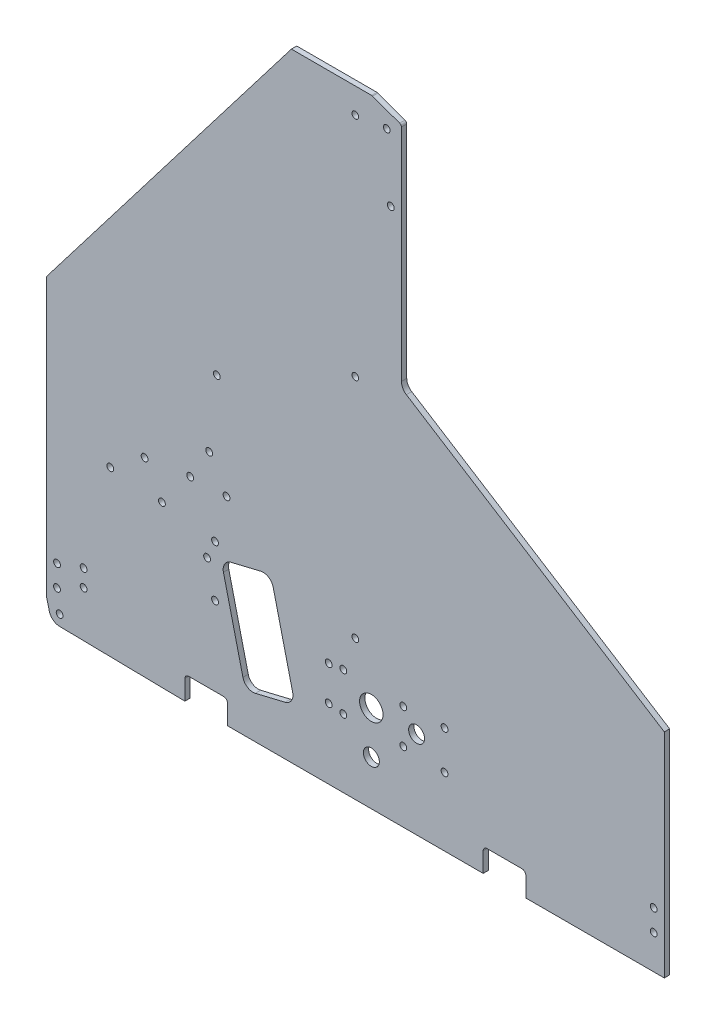
SolidWorks part; units mm, degrees
ref_plane "Front Plane" through (0, 0, 0) normal (0, 0, 1) x (1, 0, 0)
ref_plane "Top Plane" through (0, 0, 0) normal (0, 1, 0) x (1, 0, 0)
ref_plane "Right Plane" through (0, 0, 0) normal (1, 0, 0) x (0, 0, -1)
sketch "Sketch1" plane through (0, 0, 0) normal (0, 0, 1) x (1, 0, 0)
  line L0 (82.55, -20.32) -> (82.55, -6.35)
  line L2 (0, 0) -> (0, 157.48)
  line L4 (368.3, -20.32) -> (368.3, 106.68)
  line L5 (82.55, -6.35) -> (107.95, -6.35)
  line L6 (107.95, -6.35) -> (107.95, -20.32)
  line L7 (107.95, -20.32) -> (260.35, -20.32)
  line L8 (260.35, -20.32) -> (260.35, -6.35)
  line L9 (260.35, -6.35) -> (285.75, -6.35)
  line L10 (285.75, -6.35) -> (285.75, -20.32)
  line L11 (285.75, -20.32) -> (368.3, -20.32)
  line L12 (361.95, 12.7) -> (368.3, 12.7) construction
  line L13 (0, 0) -> (6.35, 0) construction
  line L14 (0.1896, -7.8901) -> (1.7771, -14.2401)
  line L15 (7.8295, -19.0491) -> (82.55, -20.32)
  line L16 (0, 0) -> (0, -6.35)
  line L17 (85.725, 97.155) -> (82.9754, 95.5675) construction
  line L18 (97.0634, 115.6163) -> (58.5686, 93.3913) construction
  line L19 (97.0634, 115.6163) -> (107.3822, 97.7437) construction
  line L20 (58.5686, 93.3913) -> (68.8873, 75.5187) construction
  line L21 (107.3822, 97.7437) -> (68.8873, 75.5187) construction
  line L22 (97.0634, 115.6163) -> (68.8873, 75.5187) construction
  line L23 (58.5686, 93.3913) -> (107.3822, 97.7437) construction
  line L24 (7.9375, -12.7) -> (95.7973, 60.4105) construction
  line L25 (184.15, 62.98) -> (184.15, 197.98) construction
  line L26 (184.15, 197.98) -> (184.15, 332.98) construction
  line L27 (355.6, 335.28) -> (330.2, 335.28) construction
  line L28 (330.2, 335.28) -> (330.2, 220.98) construction
  line L29 (330.2, 220.98) -> (355.6, 220.98) construction
  line L30 (355.6, 220.98) -> (355.6, 335.28) construction
  line L31 (184.15, 347.98) -> (184.15, 269.4703) construction
  line L32 (12.7, 335.28) -> (38.1, 335.28) construction
  line L33 (38.1, 335.28) -> (38.1, 220.98) construction
  line L34 (12.7, 220.98) -> (12.7, 335.28) construction
  line L35 (38.1, 220.98) -> (12.7, 220.98) construction
  line L36 (194.15, 347.98) -> (211.6138, 341.63)
  line L37 (184.15, 347.98) -> (146.05, 347.98)
  line L38 (184.15, 347.98) -> (194.15, 347.98)
  line L39 (348.5362, 347.98) -> (413.4623, 347.98)
  line L40 (348.5362, 347.98) -> (211.6138, 347.98) construction
  line L42 (146.05, 347.98) -> (0, 157.48)
  line L44 (211.6138, 341.63) -> (211.6138, 205.74)
  line L45 (211.6138, 205.74) -> (368.3, 106.68)
  line L46 (194.15, 347.98) -> (-141.0713, 347.98) construction
  circle A0 centre (6.35, 0) radius 2.032
  circle A1 centre (6.35, 12.7) radius 2.032
  circle A2 centre (361.95, 0) radius 2.032
  circle A3 centre (361.95, 12.7) radius 2.032
  arc A5 (1.7771, -14.2401) -> (7.8295, -19.0491) centre (7.9375, -12.7) ccw
  circle A6 centre (7.9375, -12.7) radius 2.032
  arc A7 (0, -6.35) -> (0.1896, -7.8901) centre (6.35, -6.35) ccw
  circle A8 centre (38.1, 78.105) radius 2.032
  circle A9 centre (85.725, 97.155) radius 2.032
  circle A10 centre (58.5686, 93.3913) radius 2.032
  circle A11 centre (68.8873, 75.5187) radius 2.032
  circle A12 centre (107.3822, 97.7437) radius 2.032
  circle A13 centre (97.0634, 115.6163) radius 2.032
  circle A14 centre (95.7973, 60.4105) radius 2.032
  circle A15 centre (184.15, 62.98) radius 2
  circle A16 centre (184.15, 197.98) radius 2
  circle A17 centre (184.15, 332.98) radius 2
  circle A18 centre (63.5, 316.23) radius 2.032
  circle A19 centre (101.6, 157.48) radius 2.032
  circle A20 centre (355.6, 335.28) radius 2.032
  circle A21 centre (330.2, 335.28) radius 2.032
  circle A22 centre (355.6, 220.98) radius 2.032
  circle A23 centre (330.2, 220.98) radius 2.032
  circle A24 centre (12.7, 335.28) radius 2.032
  circle A25 centre (38.1, 335.28) radius 2.032
  circle A26 centre (12.7, 220.98) radius 2.032
  circle A27 centre (38.1, 220.98) radius 2.032
  circle A28 centre (202.8819, 335.28) radius 2
  circle A29 centre (205.2638, 296.418) radius 2.032
  point P82 (184.15, 347.98)
  point P83 (202.8819, 344.805)
  dimension "D6" = 4.064
  dimension "D10" = 6.35
  dimension "D11" = 4.064
  dimension "D17" = 38.1
  dimension "D27" = 4
  dimension "D31" = 4.064
  dimension "D32" = 38.1
  dimension "D36" = 4.064
  dimension "D47" = 45.212
  dimension "D48" = 4.064
  dimension "D2" = 127
  dimension "D3" = 13.97
  dimension "D4" = 25.4
  dimension "D5" = 152.4
  dimension "D7" = 12.7
  dimension "D8" = 6.35
  dimension "D9" = 20.32
  dimension "D12" = 12.7
  dimension "D13" = 1.5875
  dimension "D14" = 82.55
  dimension "D15" = 368.3
  dimension "D16" = 6.35
  dimension "D18" = 98.425
  dimension "D19" = 47.625
  dimension "D20" = 19.05
  dimension "D21" = 3.175
  dimension "D22" = 60
  dimension "D23" = 20.6375
  dimension "D24" = 44.45
  dimension "D25" = 38.1
  dimension "D26" = 114.3
  dimension "D28" = 135
  dimension "D29" = 12.7
  dimension "D30" = 15
  dimension "D33" = 63.5
  dimension "D34" = 27.4638
  dimension "D35" = 101.6
  dimension "D37" = 114.3
  dimension "D38" = 25.4
  dimension "D39" = 12.7
  dimension "D40" = 157.48
  dimension "D41" = 142.24
  dimension "D42" = 368.3
  dimension "D43" = 10
  dimension "D44" = 6.35
  dimension "D45" = 31.75
  dimension "D46" = 6.35
  dimension "D49" = 6.35
extrude "Boss-Extrude1" add sketch "Sketch1" along normal blind 3.175 contours L16 A7 L14 A5 L15 L2 A0 A1 A6 region at (167.8922, 118.3155, 0)
fillet "Fillet1" radius 2.286 4 edges at (285.75, -6.35, 1.5875) (107.95, -6.35, 1.5875) (260.35, -6.35, 1.5875) (82.55, -6.35, 1.5875)
fillet "Fillet2" radius 6.35 1 edges at (211.6138, 205.74, 1.5875)
sketch "Sketch2" plane through (0, 0, 0) normal (0, 0, -1) x (-1, 0, 0)
  circle A0 centre (-100.5528, 71.086) radius 2.032 construction
  circle A1 centre (-100.5528, 40.606) radius 2.032 construction
  circle A2 centre (-22.225, 18.2025) radius 2.032 construction
  circle A3 centre (-22.225, 8.0425) radius 2.032 construction
  circle A4 centre (-100.5528, 71.086) radius 2.032
  circle A5 centre (-100.5528, 40.606) radius 2.032
  circle A6 centre (-22.225, 18.2025) radius 2.032
  circle A7 centre (-22.225, 8.0425) radius 2.032
extrude "Cut-Extrude1" cut sketch "Sketch2" against normal through all
fillet "Fillet3" radius 1.5875 2 edges at (211.6138, 341.63, 1.5875) (194.15, 347.98, 1.5875)
sketch "Sketch3" plane through (0, 0, 3.175) normal (0, 0, 1) x (1, 0, 0)
  line L0 (132.9524, 63.2646) -> (132.7215, 64.2281) construction
  line L1 (128.3814, 66.8897) -> (110.6828, 62.6472) construction
  line L2 (114.5132, 58.4237) -> (126.8822, 61.3887) construction
  line L3 (108.0212, 58.3071) -> (108.2522, 57.3436) construction
  line L4 (131.2006, 57.703) -> (140.0164, 20.9265) construction
  line L5 (144.0993, 16.7636) -> (132.9524, 63.2646) construction
  line L6 (108.2522, 57.3436) -> (119.3991, 10.8426) construction
  line L7 (121.1509, 16.4042) -> (112.3351, 53.1807) construction
  line L8 (119.3991, 10.8426) -> (119.6301, 9.8791) construction
  line L9 (144.3303, 15.8001) -> (144.0993, 16.7636) construction
  line L10 (137.8383, 15.6835) -> (125.4694, 12.7185) construction
  line L11 (123.9701, 7.2175) -> (141.6687, 11.4601) construction
  line L12 (132.9524, 63.2646) -> (132.7215, 64.2281)
  line L13 (128.3814, 66.8897) -> (110.6828, 62.6472)
  line L14 (114.5132, 58.4237) -> (126.8822, 61.3887)
  line L15 (108.0212, 58.3071) -> (108.2522, 57.3436)
  line L16 (131.2006, 57.703) -> (140.0164, 20.9265)
  line L17 (144.0993, 16.7636) -> (132.9524, 63.2646)
  line L18 (108.2522, 57.3436) -> (119.3991, 10.8426)
  line L19 (121.1509, 16.4042) -> (112.3351, 53.1807)
  line L20 (119.3991, 10.8426) -> (119.6301, 9.8791)
  line L21 (144.3303, 15.8001) -> (144.0993, 16.7636)
  line L22 (137.8383, 15.6835) -> (125.4694, 12.7185)
  line L23 (123.9701, 7.2175) -> (141.6687, 11.4601)
  line L24 (127.7894, 69.3598) -> (110.0908, 65.1172)
  line L25 (105.5512, 57.715) -> (105.7822, 56.7515)
  line L26 (105.7822, 56.7515) -> (116.9291, 10.2505)
  line L27 (116.9291, 10.2505) -> (117.16, 9.287)
  line L28 (124.5622, 4.7475) -> (142.2608, 8.99)
  line L29 (146.8003, 16.3922) -> (146.5694, 17.3557)
  line L30 (146.5694, 17.3557) -> (135.4225, 63.8567)
  line L31 (135.4225, 63.8567) -> (135.1915, 64.8202)
  arc A0 (132.7215, 64.2281) -> (128.6308, 66.9403) centre (129.2206, 63.3889) ccw construction
  arc A1 (110.6828, 62.6472) -> (110.4377, 62.5791) centre (111.522, 59.1463) ccw construction
  arc A2 (128.6308, 66.9403) -> (128.3814, 66.8897) centre (129.2206, 63.3889) ccw construction
  arc A3 (110.4377, 62.5791) -> (108.0212, 58.3071) centre (111.522, 59.1463) ccw construction
  arc A4 (119.6301, 9.8791) -> (123.7207, 7.1669) centre (123.1309, 10.7183) ccw construction
  arc A5 (141.9139, 11.5281) -> (144.3303, 15.8001) centre (140.8295, 14.9609) ccw construction
  arc A6 (141.6687, 11.4601) -> (141.9139, 11.5281) centre (140.8295, 14.9609) ccw construction
  arc A7 (123.7207, 7.1669) -> (123.9701, 7.2175) centre (123.1309, 10.7183) ccw construction
  arc A8 (132.7215, 64.2281) -> (128.6308, 66.9403) centre (129.2206, 63.3889) ccw
  arc A9 (110.6828, 62.6472) -> (110.4377, 62.5791) centre (111.522, 59.1463) ccw
  arc A10 (128.6308, 66.9403) -> (128.3814, 66.8897) centre (129.2206, 63.3889) ccw
  arc A11 (110.4377, 62.5791) -> (108.0212, 58.3071) centre (111.522, 59.1463) ccw
  arc A12 (119.6301, 9.8791) -> (123.7207, 7.1669) centre (123.1309, 10.7183) ccw
  arc A13 (141.9139, 11.5281) -> (144.3303, 15.8001) centre (140.8295, 14.9609) ccw
  arc A14 (141.6687, 11.4601) -> (141.9139, 11.5281) centre (140.8295, 14.9609) ccw
  arc A15 (123.7207, 7.1669) -> (123.9701, 7.2175) centre (123.1309, 10.7183) ccw
  arc A16 (110.0908, 65.1172) -> (109.6726, 65.0012) centre (111.522, 59.1463) ccw
  arc A17 (109.6726, 65.0012) -> (105.5512, 57.715) centre (111.522, 59.1463) ccw
  arc A18 (117.16, 9.287) -> (124.1369, 4.6613) centre (123.1309, 10.7183) ccw
  arc A19 (124.1369, 4.6613) -> (124.5622, 4.7475) centre (123.1309, 10.7183) ccw
  arc A20 (142.2608, 8.99) -> (142.6789, 9.1061) centre (140.8295, 14.9609) ccw
  arc A21 (142.6789, 9.1061) -> (146.8003, 16.3922) centre (140.8295, 14.9609) ccw
  arc A22 (135.1915, 64.8202) -> (128.2147, 69.446) centre (129.2206, 63.3889) ccw
  arc A23 (128.2147, 69.446) -> (127.7894, 69.3598) centre (129.2206, 63.3889) ccw
  ellipse E0 centre (124.5974, 48.8487) end of major axis (128.5376, 61.3578) minor radius 6 (131.2006, 57.703) -> (126.8822, 61.3887) ccw construction
  ellipse E1 centre (122.2349, 48.2824) end of major axis (113.0518, 57.6456) minor radius 6 (114.5132, 58.4237) -> (112.3351, 53.1807) ccw construction
  ellipse E2 centre (127.7541, 25.2585) end of major axis (131.6942, 37.7675) minor radius 6 (121.1509, 16.4042) -> (125.4694, 12.7185) ccw construction
  ellipse E3 centre (130.1166, 25.8248) end of major axis (139.2998, 16.4616) minor radius 6 (137.8383, 15.6835) -> (140.0164, 20.9265) ccw construction
  ellipse E4 centre (124.5974, 48.8487) end of major axis (120.6573, 36.3397) minor radius 6 (131.2006, 57.703) -> (126.8822, 61.3887) ccw
  ellipse E5 centre (122.2349, 48.2824) end of major axis (131.4181, 38.9192) minor radius 6 (114.5132, 58.4237) -> (112.3351, 53.1807) ccw
  ellipse E6 centre (127.7541, 25.2585) end of major axis (131.6942, 37.7675) minor radius 6 (121.1509, 16.4042) -> (125.4694, 12.7185) ccw
  ellipse E7 centre (130.1166, 25.8248) end of major axis (139.2998, 16.4616) minor radius 6 (137.8383, 15.6835) -> (140.0164, 20.9265) ccw
  dimension "D1" = 2.54
extrude "Cut-Extrude2" cut sketch "Sketch3" against normal through all contours A22 A23 L24 A16 A17 L25 L26 L27 A18 A19 L28 A20 A21 L29 L30 L31 A15 A12 L20 L18 L15 A11 A9 L13 A10 A8 L12 L17 L21 A13 A14 L23 | A12 A15 L23 A14 A13 L21 L17 L12 A8 A10 L13 A9 A11 L15 L18 L20 E7 L22 E6 L19 E5 L14 E4 L16 | L22 E7 L16 E4 L14 E5 L19 E6 region at (137.844, 39.8506, 3.175) region at (126.1758, 37.0536, 3.175) region at (128.1544, 68.6507, 3.175)
sketch "Sketch4" plane through (0, 0, 3.175) normal (0, 0, 1) x (1, 0, 0)
  line L0 (107.3822, 97.7437) -> (68.8873, 75.5187) construction
  line L1 (168.275, 21.4312) -> (212.725, 21.4312) construction
  line L2 (168.275, 21.4312) -> (168.275, 42.0687) construction
  line L3 (168.275, 42.0687) -> (212.725, 42.0687) construction
  line L4 (212.725, 21.4312) -> (212.725, 42.0687) construction
  line L5 (168.275, 21.4312) -> (212.725, 42.0687) construction
  line L6 (168.275, 42.0687) -> (212.725, 21.4312) construction
  line L7 (97.0634, 115.6163) -> (107.3822, 97.7437) construction
  line L8 (107.95, -20.32) -> (260.35, -20.32) construction
  line L9 (193.675, 31.75) -> (177.005, 31.75) construction
  line L10 (190.5, 31.75) -> (193.675, 31.75) construction
  line L11 (6.35, 12.7) -> (361.95, 12.7) construction
  line L12 (107.95, -6.35) -> (107.95, -20.32) construction
  line L13 (193.675, 31.75) -> (220.6625, 31.75) construction
  line L14 (177.005, 20.2819) -> (177.005, 43.2181) construction
  line L15 (194.15, 47.98) -> (174.15, 47.98) construction
  line L16 (194.15, 47.98) -> (194.15, 347.98) construction
  line L17 (194.15, 347.98) -> (174.15, 347.98) construction
  line L18 (174.15, 47.98) -> (174.15, 347.98) construction
  line L19 (194.15, 47.98) -> (174.15, 347.98) construction
  line L20 (194.15, 347.98) -> (174.15, 47.98) construction
  circle A0 centre (168.275, 42.0687) radius 2.032
  circle A1 centre (212.725, 42.0687) radius 2.032
  circle A2 centre (212.725, 21.4312) radius 2.032
  circle A3 centre (168.275, 21.4312) radius 2.032
  circle A4 centre (193.675, 31.75) radius 6.985
  circle A5 centre (220.6625, 31.75) radius 4.7625
  circle A7 centre (220.6625, 31.75) radius 14.2875 construction
  circle A8 centre (193.675, 31.75) radius 12.7 construction
  circle A9 centre (177.005, 43.2181) radius 2.032
  circle A10 centre (177.005, 20.2819) radius 2.032
  circle A11 centre (237.33, 43.2181) radius 2.032
  circle A12 centre (237.33, 20.2819) radius 2.032
  circle A13 centre (193.675, 6.35) radius 4.7625
  point P0 (190.5, 31.75)
  point P26 (184.15, 197.98)
  point P38 (177.005, 31.75)
  point P46 (0, 0)
  point P47 (0, 0)
  dimension "D1" = 4.064
  dimension "D4" = 13.97
  dimension "D7" = 9.525
  dimension "D10" = 25.4
  dimension "D11" = 28.575
  dimension "D2" = 52.07
  dimension "D3" = 3.175
  dimension "D5" = 82.55
  dimension "D6" = 26.9875
  dimension "D8" = 20
  dimension "D9" = 300
  dimension "D12" = 16.67
  dimension "D13" = 22.9362
  dimension "D14" = 60.325
  dimension "D15" = 25.4
extrude "Cut-Extrude3" cut sketch "Sketch4" against normal through all
